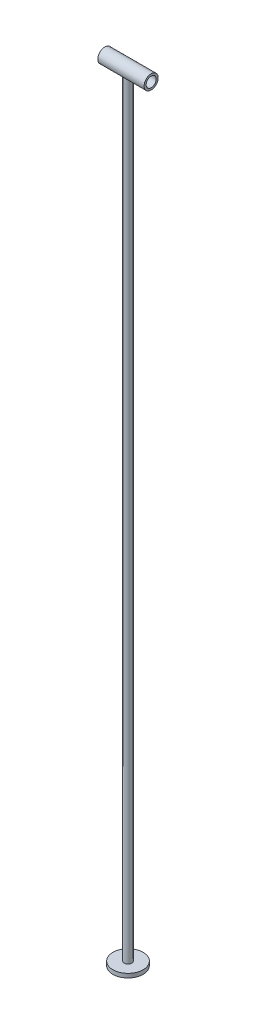
SolidWorks part; units mm, degrees
material "Plain Carbon Steel"
ref_plane "Front Plane" through (0, 0, 0) normal (0, 0, 1) x (1, 0, 0)
ref_plane "Top Plane" through (0, 0, 0) normal (0, 1, 0) x (1, 0, 0)
ref_plane "Right Plane" through (0, 0, 0) normal (1, 0, 0) x (0, 0, -1)
sketch "klip_Sketch1" plane through (0, 0, 0) normal (0, 1, 0) x (1, 0, 0)
  circle A0 centre (0, 0) radius 75
  dimension "D1" = 150
extrude "klip_Boss-Extrude1" add sketch "klip_Sketch1" against normal blind 20 contours A0
sketch "klip_Sketch3" plane through (0, 0, 0) normal (1, 0, 0) x (0, 0, -1)
  circle A0 centre (0, 3835) radius 35
  circle A1 centre (0, 3835) radius 25
  dimension "D3" = 50
  dimension "D1" = 70
  dimension "D2" = 3835
extrude "klip_Boss-Extrude3" add sketch "klip_Sketch3" along normal blind 115 and the other way blind 115 separate body
sketch "klip_Sketch2" plane through (0, 0, 0) normal (0, 1, 0) x (1, 0, 0)
  circle A0 centre (0, 0) radius 18.75
  dimension "D1" = 37.5
extrude "klip_Boss-Extrude2" add sketch "klip_Sketch2" along normal up to surface (3805.446 mm away) contours A0 up to face at (-115, 3835, -35)
equation "\"sirina_klipa\"= 150"
equation "\"debljina_klipa\"= 20"
equation "\"sirina_klipnjace\"= \"sirina_klipa\" / 4"
equation "\"duljina_klipnjace\" = 3800"
equation "\"r2_v\"= 70"
equation "\"r2_u\"= 50"
equation "\"r1_v\"= 70"
equation "\"r1_u\"= 50"
equation "\"l2\" = 230"
equation "\"l1\" = 270"
equation "\"sirina_cilindra\"= \"sirina_klipa\" + \"debljina_stijenke\" * 2"
equation "\"duljina_komore\"= 30"
equation "\"debljina_stijenke\"= 10"
equation "\"D3@cilindar_Sketch1\"= \"duljina_komore\""
equation "\"D4@cilindar_Sketch1\"=\"sirina_klipa\"/2"
equation "\"D1@cilindar_Sketch1\"=\"sirina_cilindra\"/2"
equation "\"D2@cilindar_Sketch1\"= \"duljina_cilindra\""
equation "\"D1@cilindar_Shell1\"=\"debljina_stijenke\""
equation "\"duljina_cilindra\"= \"duljina_klipnjace\" + \"debljina_klipa\" + \"debljina_stijenke\" - \"duljina_komore\""
equation "\"D1@cilindar_Sketch2\"=\"duljina_cilindra\"/2 + \"duljina_komore\" + \"r1_v\"/2 + 1"
equation "\"D2@cilindar_Sketch2\"=\"r1_v\""
equation "\"D3@cilindar_Sketch2\"=\"r1_u\""
equation "\"D1@cilindar_Sketch7\" = \"sirina_klipnjace\""
equation "\"D2@cilindar_Boss-Extrude1\"=\"l1\"/2"
equation "\"D1@cilindar_Boss-Extrude1\"=\"l1\"/2"
equation "\"D1@klip_Boss-Extrude1\"=\"debljina_klipa\""
equation "\"D1@klip_Sketch1\"=\"sirina_klipa\""
equation "\"D2@klip_Sketch3\"= \"duljina_klipnjace\" + \"r2_v\" / 2"
equation "\"D3@klip_Sketch3\" = \"r2_u\""
equation "\"D1@klip_Sketch3\"=\"r2_v\""
equation "\"D1@klip_Boss-Extrude3\" = \"l2\" / 2"
equation "\"D2@klip_Boss-Extrude3\"= \"l2\" / 2"
equation "\"D1@klip_Sketch2\"=\"sirina_klipnjace\""
